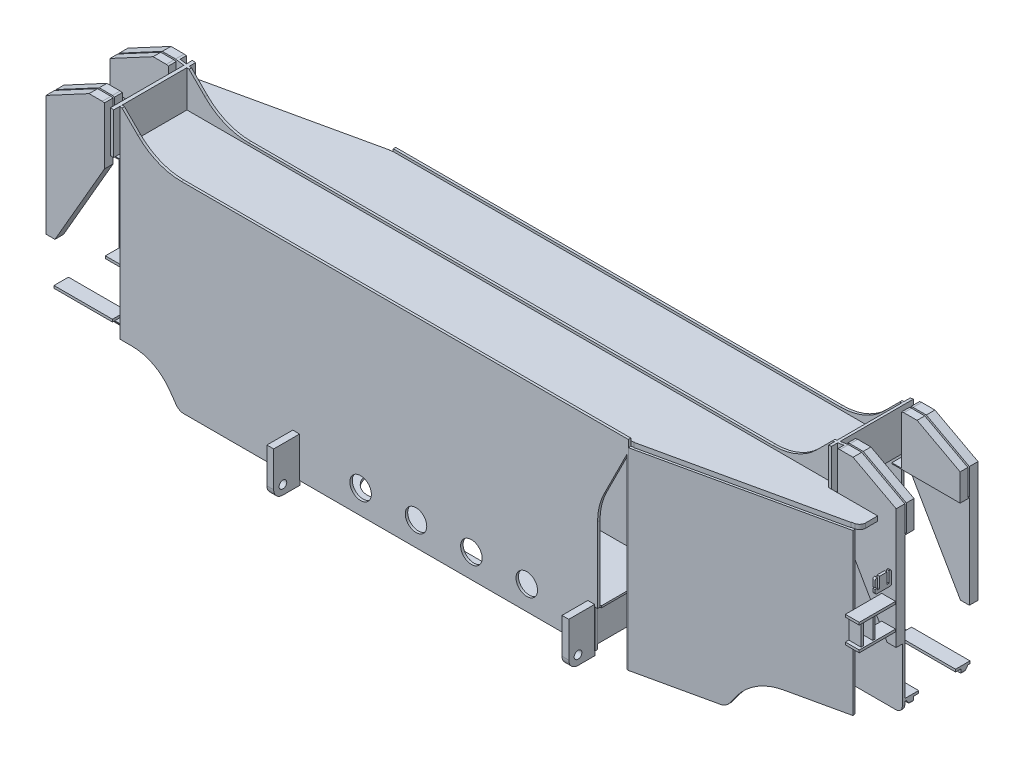
SolidWorks part; units mm, degrees
ref_plane "正面" through (0, 0, 0) normal (0, 0, 1) x (1, 0, 0)
ref_plane "平面" through (0, 0, 0) normal (0, 1, 0) x (1, 0, 0)
ref_plane "右側面" through (0, 0, 0) normal (1, 0, 0) x (0, 0, -1)
ref_plane "平面1" through (0, 0, 238) normal (0, 0, 1) x (1, 0, 0)
sketch "ｽｹｯﾁ2" plane through (0, 0, 238) normal (0, 0, 1) x (1, 0, 0)
  line L0 (20, 120) -> (259.781, 119.9998)
  line L1 (382.7741, 55.8641) -> (403.0452, 26.8271)
  line L2 (427.644, 13.9998) -> (2117.356, 13.9998)
  line L3 (2141.9548, 26.8271) -> (2162.2259, 55.8641)
  line L4 (2285.219, 119.9998) -> (2525, 120)
  line L5 (2545, 140) -> (2545, 315.36)
  line L6 (2545, 315.36) -> (2545, 706)
  line L7 (2545, 706) -> (2405, 781)
  line L8 (2405, 781) -> (2362, 781)
  line L9 (2362, 781) -> (2318, 774)
  line L10 (2318, 774) -> (2266.5789, 722.5791)
  line L11 (2125.157, 663.9999) -> (419.843, 663.9999)
  line L12 (278.4211, 722.5791) -> (227, 774)
  line L13 (227, 774) -> (183, 781)
  line L14 (183, 781) -> (140, 781)
  line L15 (140, 781) -> (0, 706)
  line L16 (0, 706) -> (0, 315.36)
  line L17 (0, 315.36) -> (0, 140)
  arc A0 (0, 140) -> (20, 120) centre (20, 140) ccw
  arc A1 (259.781, 119.9998) -> (382.7741, 55.8641) centre (259.781, -30) cw
  arc A2 (403.0452, 26.8271) -> (427.644, 13.9998) centre (427.644, 44) ccw
  arc A3 (2117.356, 13.9998) -> (2141.9548, 26.8271) centre (2117.356, 44) ccw
  arc A4 (2162.2259, 55.8641) -> (2285.219, 119.9998) centre (2285.219, -30) cw
  arc A5 (2525, 120) -> (2545, 140) centre (2525, 140) ccw
  arc A6 (2266.5789, 722.5791) -> (2125.157, 663.9999) centre (2125.157, 864) cw
  arc A7 (419.843, 663.9999) -> (278.4211, 722.5791) centre (419.843, 864) cw
extrude "ﾎﾞｽ - 押し出し1" add sketch "ｽｹｯﾁ2" along normal blind 8
sketch "ｽｹｯﾁ3" plane through (0, 0, 238) normal (0, 0, 1) x (1, 0, 0)
  line L0 (1072.5, 297) -> (1472.5, 297)
  line L1 (1472.5, 497) -> (1072.5, 497)
  circle A0 centre (972.5, 92) radius 35
  circle A1 centre (1272.5, 92) radius 35
  circle A2 centre (1572.5, 92) radius 35
  arc A3 (1472.5, 297) -> (1572.5, 397) centre (1472.5, 397) ccw
  arc A4 (1572.5, 397) -> (1472.5, 497) centre (1472.5, 397) ccw
  arc A5 (1072.5, 497) -> (972.5, 397) centre (1072.5, 397) ccw
  arc A6 (972.5, 397) -> (1072.5, 297) centre (1072.5, 397) ccw
  circle A7 centre (50, 499) radius 20.25
  circle A8 centre (2495, 499) radius 20.25
  circle A9 centre (27, 401.5) radius 10.5
  circle A10 centre (2518, 401.5) radius 10.5
sketch "ｽｹｯﾁ4" plane through (0, 0, 238) normal (0, 0, 1) x (1, 0, 0)
  line L0 (1072.5, 297) -> (1472.5, 297)
  line L1 (1472.5, 497) -> (1072.5, 497)
  circle A0 centre (972.5, 92) radius 35
  circle A1 centre (1272.5, 92) radius 35
  circle A2 centre (1572.5, 92) radius 35
  arc A3 (1472.5, 297) -> (1572.5, 397) centre (1472.5, 397) ccw
  arc A4 (1572.5, 397) -> (1472.5, 497) centre (1472.5, 397) ccw
  arc A5 (1072.5, 497) -> (972.5, 397) centre (1072.5, 397) ccw
  arc A6 (972.5, 397) -> (1072.5, 297) centre (1072.5, 397) ccw
  circle A7 centre (50, 499) radius 20.25
  circle A8 centre (2495, 499) radius 20.25
  circle A9 centre (27, 401.5) radius 10.5
  circle A10 centre (2518, 401.5) radius 10.5
extrude "ｶｯﾄ - 押し出し2" cut sketch "ｽｹｯﾁ4" along normal blind 8
ref_plane "平面2" through (0, 0, 20) normal (0, 0, 1) x (1, 0, 0)
sketch "ｽｹｯﾁ6" plane through (0, 0, 20) normal (0, 0, 1) x (1, 0, 0)
  line L0 (781, 14) -> (2117.356, 13.9998)
  line L1 (2141.9548, 26.8271) -> (2162.2259, 55.8641)
  line L2 (2285.219, 119.9998) -> (2325, 120)
  line L3 (2325, 120) -> (2325, 775.1136)
  line L4 (2325, 775.1136) -> (2318, 774)
  line L5 (2318, 774) -> (2266.5789, 722.5791)
  line L6 (2125.157, 663.9999) -> (672.5, 664)
  line L7 (672.5, 664) -> (672.5, 629)
  line L8 (672.5, 629) -> (751.3851, 471.2291)
  line L9 (772.4999, 381.786) -> (772.5, 138)
  line L10 (772.5, 138) -> (781, 138)
  line L11 (781, 138) -> (781, 14)
  arc A0 (2117.356, 13.9998) -> (2141.9548, 26.8271) centre (2117.356, 44) ccw
  arc A1 (2162.2259, 55.8641) -> (2285.219, 119.9998) centre (2285.219, -30) cw
  arc A2 (2266.5789, 722.5791) -> (2125.157, 663.9999) centre (2125.157, 864) cw
  arc A3 (751.3851, 471.2291) -> (772.4999, 381.786) centre (572.5, 381.786) cw
extrude "ﾎﾞｽ - 押し出し2" add sketch "ｽｹｯﾁ6" along normal blind 8
sketch "ｽｹｯﾁ7" plane through (0, 0, 20) normal (0, 0, 1) x (1, 0, 0)
  circle A0 centre (1002.5, 92) radius 35
  circle A1 centre (1182.5, 92) radius 35
  circle A2 centre (1362.5, 92) radius 35
  circle A3 centre (1542.5, 92) radius 35
sketch "ｽｹｯﾁ8" plane through (0, 0, 20) normal (0, 0, 1) x (1, 0, 0)
  circle A0 centre (1002.5, 92) radius 35
  circle A1 centre (1182.5, 92) radius 35
  circle A2 centre (1362.5, 92) radius 35
  circle A3 centre (1542.5, 92) radius 35
extrude "ｶｯﾄ - 押し出し4" cut sketch "ｽｹｯﾁ8" along normal blind 8
ref_plane "平面3" through (0, 0, 456) normal (0, 0, 1) x (1, 0, 0)
sketch "ｽｹｯﾁ10" plane through (0, 0, 456) normal (0, 0, 1) x (1, 0, 0)
  line L0 (1764, 14) -> (1764, 138)
  line L1 (1764, 138) -> (1772.5, 138)
  line L2 (1772.5, 138) -> (1772.5001, 381.786)
  line L3 (1793.6149, 471.2291) -> (1872.5, 629)
  line L4 (1872.5, 629) -> (1872.5, 664)
  line L5 (1872.5, 664) -> (419.843, 663.9999)
  line L6 (278.4211, 722.5791) -> (227, 774)
  line L7 (227, 774) -> (220, 775.1136)
  line L8 (220, 775.1136) -> (220, 120)
  line L9 (220, 120) -> (259.781, 119.9998)
  line L10 (382.7741, 55.8641) -> (403.0452, 26.8271)
  line L11 (427.644, 13.9998) -> (1764, 14)
  arc A0 (1772.5001, 381.786) -> (1793.6149, 471.2291) centre (1972.5, 381.786) cw
  arc A1 (419.843, 663.9999) -> (278.4211, 722.5791) centre (419.843, 864) cw
  arc A2 (259.781, 119.9998) -> (382.7741, 55.8641) centre (259.781, -30) cw
  arc A3 (403.0452, 26.8271) -> (427.644, 13.9998) centre (427.644, 44) ccw
extrude "ﾎﾞｽ - 押し出し3" add sketch "ｽｹｯﾁ10" along normal blind 8
sketch "ｽｹｯﾁ11" plane through (0, 0, 456) normal (0, 0, 1) x (1, 0, 0)
  circle A0 centre (1002.5, 92) radius 35
  circle A1 centre (1182.5, 92) radius 35
  circle A2 centre (1362.5, 92) radius 35
  circle A3 centre (1542.5, 92) radius 35
sketch "ｽｹｯﾁ12" plane through (0, 0, 456) normal (0, 0, 1) x (1, 0, 0)
  circle A0 centre (1002.5, 92) radius 35
  circle A1 centre (1182.5, 92) radius 35
  circle A2 centre (1362.5, 92) radius 35
  circle A3 centre (1542.5, 92) radius 35
extrude "ｶｯﾄ - 押し出し6" cut sketch "ｽｹｯﾁ12" along normal blind 8
ref_plane "平面4" through (0, 14, 0) normal (0, 1, 0) x (1, 0, 0)
sketch "ｽｹｯﾁ14" plane through (0, 14, 0) normal (0, 1, 0) x (1, 0, 0)
  line L0 (678.3594, -26.7085) -> (75.7, -159.54)
  line L1 (75.7, -159.54) -> (73.9781, -151.7275)
  line L2 (73.9781, -151.7275) -> (671.6288, -20)
  line L3 (671.6288, -20) -> (676.8807, -20)
  line L4 (676.8807, -20) -> (678.3594, -26.7085)
extrude "ﾎﾞｽ - 押し出し4" add sketch "ｽｹｯﾁ14" along normal blind 626.98
sketch "ｽｹｯﾁ15" plane through (0, 14, 0) normal (0, 1, 0) x (1, 0, 0)
  line L0 (1866.6406, -457.2915) -> (2469.3, -324.46)
  line L1 (2469.3, -324.46) -> (2471.0219, -332.2725)
  line L2 (2471.0219, -332.2725) -> (1873.3712, -464)
  line L3 (1873.3712, -464) -> (1868.1193, -464)
  line L4 (1868.1193, -464) -> (1866.6406, -457.2915)
extrude "ﾎﾞｽ - 押し出し5" add sketch "ｽｹｯﾁ15" along normal blind 626.98
ref_plane "平面5" through (0, 600, 0) normal (0, 1, 0) x (1, 0, 0)
sketch "ｽｹｯﾁ17" plane through (0, 600, 0) normal (0, 1, 0) x (1, 0, 0)
  line L0 (662.5192, -29.1759) -> (85.2504, -156.411)
  line L1 (85.2504, -156.411) -> (85.6808, -158.3641)
  line L2 (85.6808, -158.3641) -> (662.9496, -31.129)
  line L3 (662.9496, -31.129) -> (662.5192, -29.1759)
extrude "ﾎﾞｽ - 押し出し6" add sketch "ｽｹｯﾁ17" along normal blind 56
sketch "ｽｹｯﾁ18" plane through (0, 600, 0) normal (0, 1, 0) x (1, 0, 0)
  line L0 (1882.4808, -454.8241) -> (2459.7496, -327.589)
  line L1 (2459.7496, -327.589) -> (2459.3192, -325.6359)
  line L2 (2459.3192, -325.6359) -> (1882.0504, -452.871)
  line L3 (1882.0504, -452.871) -> (1882.4808, -454.8241)
extrude "ﾎﾞｽ - 押し出し7" add sketch "ｽｹｯﾁ18" along normal blind 56
ref_plane "平面6" through (0, 641, 0) normal (0, 1, 0) x (1, 0, 0)
sketch "ｽｹｯﾁ20" plane through (0, 641, 0) normal (0, 1, 0) x (1, 0, 0)
  line L0 (672.5, -28) -> (75.7206, -159.5325)
  line L1 (59.9974, -179.072) -> (60, -218)
  line L2 (60, -218) -> (220, -218)
  line L3 (220, -218) -> (220, -238)
  line L4 (220, -238) -> (2324.98, -238)
  line L5 (2324.98, -238) -> (2324.98, -28)
  line L6 (2324.98, -28) -> (672.5, -28)
  arc A0 (75.7206, -159.5325) -> (59.9974, -179.072) centre (80, -179.072) ccw
extrude "ﾎﾞｽ - 押し出し8" add sketch "ｽｹｯﾁ20" along normal blind 15
sketch "ｽｹｯﾁ21" plane through (0, 641, 0) normal (0, 1, 0) x (1, 0, 0)
  line L0 (1872.5, -456) -> (2469.2794, -324.4675)
  line L1 (2485.0026, -304.928) -> (2485, -266)
  line L2 (2485, -266) -> (2325, -266)
  line L3 (2325, -266) -> (2325, -246)
  line L4 (2325, -246) -> (220.02, -246)
  line L5 (220.02, -246) -> (220.02, -456)
  line L6 (220.02, -456) -> (1872.5, -456)
  arc A0 (2469.2794, -324.4675) -> (2485.0026, -304.928) centre (2465, -304.928) ccw
extrude "ﾎﾞｽ - 押し出し9" add sketch "ｽｹｯﾁ21" along normal blind 15
ref_plane "平面7" through (0, 22, 0) normal (0, 1, 0) x (1, 0, 0)
sketch "ｽｹｯﾁ23" plane through (0, 22, 0) normal (0, 1, 0) x (1, 0, 0)
  line L0 (804, -28) -> (2098.5, -28)
  line L1 (2098.5, -28) -> (2098.5, -238)
  line L2 (2098.5, -238) -> (804, -238)
  line L3 (804, -238) -> (804, -28)
extrude "ﾎﾞｽ - 押し出し10" add sketch "ｽｹｯﾁ23" along normal blind 8
sketch "ｽｹｯﾁ24" plane through (0, 22, 0) normal (0, 1, 0) x (1, 0, 0)
  line L0 (1202, -73) -> (1342, -73)
  line L1 (1342, -193) -> (1202, -193)
  circle A0 centre (972, -133) radius 60
  circle A1 centre (1572, -133) radius 60
  circle A2 centre (1942, -133) radius 60
  arc A3 (1342, -73) -> (1402, -133) centre (1342, -133) cw
  arc A4 (1402, -133) -> (1342, -193) centre (1342, -133) cw
  arc A5 (1202, -193) -> (1142, -133) centre (1202, -133) cw
  arc A6 (1142, -133) -> (1202, -73) centre (1202, -133) cw
sketch "ｽｹｯﾁ25" plane through (0, 22, 0) normal (0, 1, 0) x (1, 0, 0)
  line L0 (1202, -73) -> (1342, -73)
  line L1 (1342, -193) -> (1202, -193)
  circle A0 centre (972, -133) radius 60
  circle A1 centre (1572, -133) radius 60
  circle A2 centre (1942, -133) radius 60
  arc A3 (1342, -73) -> (1402, -133) centre (1342, -133) cw
  arc A4 (1402, -133) -> (1342, -193) centre (1342, -133) cw
  arc A5 (1202, -193) -> (1142, -133) centre (1202, -133) cw
  arc A6 (1142, -133) -> (1202, -73) centre (1202, -133) cw
extrude "ｶｯﾄ - 押し出し8" cut sketch "ｽｹｯﾁ25" along normal blind 8
sketch "ｽｹｯﾁ26" plane through (0, 22, 0) normal (0, 1, 0) x (1, 0, 0)
  line L0 (446.5, -246) -> (1741, -246)
  line L1 (1741, -246) -> (1741, -456)
  line L2 (1741, -456) -> (446.5, -456)
  line L3 (446.5, -456) -> (446.5, -246)
extrude "ﾎﾞｽ - 押し出し11" add sketch "ｽｹｯﾁ26" along normal blind 8
sketch "ｽｹｯﾁ27" plane through (0, 22, 0) normal (0, 1, 0) x (1, 0, 0)
  line L0 (1203, -291) -> (1343, -291)
  line L1 (1343, -411) -> (1203, -411)
  circle A0 centre (603, -351) radius 60
  circle A1 centre (973, -351) radius 60
  circle A2 centre (1573, -351) radius 60
  arc A3 (1343, -291) -> (1403, -351) centre (1343, -351) cw
  arc A4 (1403, -351) -> (1343, -411) centre (1343, -351) cw
  arc A5 (1203, -411) -> (1143, -351) centre (1203, -351) cw
  arc A6 (1143, -351) -> (1203, -291) centre (1203, -351) cw
extrude "ｶｯﾄ - 押し出し9" cut sketch "ｽｹｯﾁ27" along normal blind 8
ref_plane "平面8" through (0, 138, 0) normal (0, 1, 0) x (1, 0, 0)
sketch "ｽｹｯﾁ29" plane through (0, 138, 0) normal (0, 1, 0) x (1, 0, 0)
  line L0 (768, -28) -> (1712, -28)
  line L1 (1712, -28) -> (1712, -238)
  line L2 (1712, -238) -> (768, -238)
  line L3 (768, -238) -> (768, -28)
extrude "ﾎﾞｽ - 押し出し12" add sketch "ｽｹｯﾁ29" along normal blind 6
sketch "ｽｹｯﾁ30" plane through (0, 138, 0) normal (0, 1, 0) x (1, 0, 0)
  line L0 (833, -246) -> (1777, -246)
  line L1 (1777, -246) -> (1777, -456)
  line L2 (1777, -456) -> (833, -456)
  line L3 (833, -456) -> (833, -246)
extrude "ﾎﾞｽ - 押し出し13" add sketch "ｽｹｯﾁ30" along normal blind 6
ref_plane "平面9" through (0, 0, 218) normal (0, 0, 1) x (1, 0, 0)
sketch "ｽｹｯﾁ32" plane through (0, 0, 218) normal (0, 0, 1) x (1, 0, 0)
  line L0 (0, 315.36) -> (29.1052, 315.36)
  line L1 (29.1052, 315.36) -> (190, 594.038)
  line L2 (190, 594.038) -> (190, 779.8864)
  line L3 (190, 779.8864) -> (183, 781)
  line L4 (183, 781) -> (140, 781)
  line L5 (140, 781) -> (0, 706)
  line L6 (0, 706) -> (0, 315.36)
extrude "ﾎﾞｽ - 押し出し14" add sketch "ｽｹｯﾁ32" along normal blind 20
ref_plane "平面10" through (0, 0, 464) normal (0, 0, 1) x (1, 0, 0)
sketch "ｽｹｯﾁ34" plane through (0, 0, 464) normal (0, 0, 1) x (1, 0, 0)
  line L0 (0, 315.36) -> (29.1052, 315.36)
  line L1 (29.1052, 315.36) -> (190, 594.038)
  line L2 (190, 594.038) -> (190, 779.8864)
  line L3 (190, 779.8864) -> (183, 781)
  line L4 (183, 781) -> (140, 781)
  line L5 (140, 781) -> (0, 706)
  line L6 (0, 706) -> (0, 315.36)
extrude "ﾎﾞｽ - 押し出し15" add sketch "ｽｹｯﾁ34" along normal blind 20
sketch "ｽｹｯﾁ35" plane through (0, 0, 0) normal (0, 0, 1) x (1, 0, 0)
  line L0 (2545, 315.36) -> (2545, 706)
  line L1 (2545, 706) -> (2405, 781)
  line L2 (2405, 781) -> (2362, 781)
  line L3 (2362, 781) -> (2355, 779.8864)
  line L4 (2355, 779.8864) -> (2355, 594.038)
  line L5 (2355, 594.038) -> (2515.8948, 315.36)
  line L6 (2515.8948, 315.36) -> (2545, 315.36)
extrude "ﾎﾞｽ - 押し出し16" add sketch "ｽｹｯﾁ35" along normal blind 20
ref_plane "平面11" through (0, 0, 246) normal (0, 0, 1) x (1, 0, 0)
sketch "ｽｹｯﾁ37" plane through (0, 0, 246) normal (0, 0, 1) x (1, 0, 0)
  line L0 (2545, 315.36) -> (2545, 706)
  line L1 (2545, 706) -> (2405, 781)
  line L2 (2405, 781) -> (2362, 781)
  line L3 (2362, 781) -> (2355, 779.8864)
  line L4 (2355, 779.8864) -> (2355, 594.038)
  line L5 (2355, 594.038) -> (2515.8948, 315.36)
  line L6 (2515.8948, 315.36) -> (2545, 315.36)
extrude "ﾎﾞｽ - 押し出し17" add sketch "ｽｹｯﾁ37" along normal blind 20
ref_plane "平面12" through (0, 0, 20) normal (0, 0, 1) x (1, 0, 0)
sketch "ｽｹｯﾁ39" plane through (0, 0, 20) normal (0, 0, 1) x (1, 0, 0)
  line L0 (2545, 315.36) -> (2545, 706)
  line L1 (2545, 706) -> (2405, 781)
  line L2 (2405, 781) -> (2362, 781)
  line L3 (2362, 781) -> (2355, 779.8864)
  line L4 (2355, 779.8864) -> (2355, 594.038)
  line L5 (2355, 594.038) -> (2515.8948, 315.36)
  line L6 (2515.8948, 315.36) -> (2545, 315.36)
extrude "ﾎﾞｽ - 押し出し18" add sketch "ｽｹｯﾁ39" along normal blind 8
ref_plane "平面13" through (0, 0, 456) normal (0, 0, 1) x (1, 0, 0)
sketch "ｽｹｯﾁ41" plane through (0, 0, 456) normal (0, 0, 1) x (1, 0, 0)
  line L0 (0, 315.36) -> (29.1052, 315.36)
  line L1 (29.1052, 315.36) -> (190, 594.038)
  line L2 (190, 594.038) -> (190, 779.8864)
  line L3 (190, 779.8864) -> (183, 781)
  line L4 (183, 781) -> (140, 781)
  line L5 (140, 781) -> (0, 706)
  line L6 (0, 706) -> (0, 315.36)
extrude "ﾎﾞｽ - 押し出し19" add sketch "ｽｹｯﾁ41" along normal blind 8
ref_plane "平面14" through (0, 0, 251) normal (0, 0, 1) x (1, 0, 0)
sketch "ｽｹｯﾁ43" plane through (0, 0, 251) normal (0, 0, 1) x (1, 0, 0)
  line L0 (0, 620.82) -> (190, 620.82)
  line L1 (190, 620.82) -> (190, 779.8864)
  line L2 (190, 779.8864) -> (183, 781)
  line L3 (183, 781) -> (140, 781)
  line L4 (140, 781) -> (0, 706)
  line L5 (0, 706) -> (0, 620.82)
extrude "ﾎﾞｽ - 押し出し20" add sketch "ｽｹｯﾁ43" along normal blind 25
ref_plane "平面15" through (0, 0, 426) normal (0, 0, 1) x (1, 0, 0)
sketch "ｽｹｯﾁ45" plane through (0, 0, 426) normal (0, 0, 1) x (1, 0, 0)
  line L0 (0, 620.82) -> (190, 620.82)
  line L1 (190, 620.82) -> (190, 779.8864)
  line L2 (190, 779.8864) -> (183, 781)
  line L3 (183, 781) -> (140, 781)
  line L4 (140, 781) -> (0, 706)
  line L5 (0, 706) -> (0, 620.82)
extrude "ﾎﾞｽ - 押し出し21" add sketch "ｽｹｯﾁ45" along normal blind 25
ref_plane "平面16" through (0, 0, 33) normal (0, 0, 1) x (1, 0, 0)
sketch "ｽｹｯﾁ47" plane through (0, 0, 33) normal (0, 0, 1) x (1, 0, 0)
  line L0 (2545, 620.82) -> (2545, 706)
  line L1 (2545, 706) -> (2405, 781)
  line L2 (2405, 781) -> (2362, 781)
  line L3 (2362, 781) -> (2355, 779.8864)
  line L4 (2355, 779.8864) -> (2355, 620.82)
  line L5 (2355, 620.82) -> (2545, 620.82)
extrude "ﾎﾞｽ - 押し出し22" add sketch "ｽｹｯﾁ47" along normal blind 25
ref_plane "平面17" through (0, 0, 208) normal (0, 0, 1) x (1, 0, 0)
sketch "ｽｹｯﾁ49" plane through (0, 0, 208) normal (0, 0, 1) x (1, 0, 0)
  line L0 (2545, 620.82) -> (2545, 706)
  line L1 (2545, 706) -> (2405, 781)
  line L2 (2405, 781) -> (2362, 781)
  line L3 (2362, 781) -> (2355, 779.8864)
  line L4 (2355, 779.8864) -> (2355, 620.82)
  line L5 (2355, 620.82) -> (2545, 620.82)
extrude "ﾎﾞｽ - 押し出し23" add sketch "ｽｹｯﾁ49" along normal blind 25
sketch "ｽｹｯﾁ50" plane through (0, 0, 246) normal (0, 0, 1) x (1, 0, 0)
  line L0 (0, 617.82) -> (190, 617.82)
  line L1 (190, 617.82) -> (190, 620.82)
  line L2 (190, 620.82) -> (0, 620.82)
  line L3 (0, 620.82) -> (0, 617.82)
extrude "ﾎﾞｽ - 押し出し24" add sketch "ｽｹｯﾁ50" along normal blind 30
sketch "ｽｹｯﾁ51" plane through (0, 0, 426) normal (0, 0, 1) x (1, 0, 0)
  line L0 (0, 617.82) -> (222, 617.82)
  line L1 (222, 617.82) -> (222, 620.82)
  line L2 (222, 620.82) -> (0, 620.82)
  line L3 (0, 620.82) -> (0, 617.82)
extrude "ﾎﾞｽ - 押し出し25" add sketch "ｽｹｯﾁ51" along normal blind 32
ref_plane "平面18" through (0, 0, 26) normal (0, 0, 1) x (1, 0, 0)
sketch "ｽｹｯﾁ53" plane through (0, 0, 26) normal (0, 0, 1) x (1, 0, 0)
  line L0 (2323, 617.82) -> (2545, 617.82)
  line L1 (2545, 617.82) -> (2545, 620.82)
  line L2 (2545, 620.82) -> (2323, 620.82)
  line L3 (2323, 620.82) -> (2323, 617.82)
extrude "ﾎﾞｽ - 押し出し26" add sketch "ｽｹｯﾁ53" along normal blind 32
sketch "ｽｹｯﾁ54" plane through (0, 0, 208) normal (0, 0, 1) x (1, 0, 0)
  line L0 (2355, 617.82) -> (2545, 617.82)
  line L1 (2545, 617.82) -> (2545, 620.82)
  line L2 (2545, 620.82) -> (2355, 620.82)
  line L3 (2355, 620.82) -> (2355, 617.82)
extrude "ﾎﾞｽ - 押し出し27" add sketch "ｽｹｯﾁ54" along normal blind 30
sketch "ｽｹｯﾁ55" plane through (0, 0, 0) normal (1, 0, 0) x (0, 0, -1)
  line L0 (-251.6, 150) -> (-450.4, 150)
  line L1 (-450.4, 150) -> (-450.4, 149)
  line L2 (-450.4, 149) -> (-442.698, 138)
  line L3 (-442.698, 138) -> (-259.302, 138)
  line L4 (-259.302, 138) -> (-251.6, 149)
  line L5 (-251.6, 149) -> (-251.6, 150)
extrude "ﾎﾞｽ - 押し出し28" add sketch "ｽｹｯﾁ55" along normal blind 346.3065
sketch "ｽｹｯﾁ56" plane through (0, 138, 0) normal (0, 1, 0) x (1, 0, 0)
  line L0 (-10, -273.771) -> (155, -273.771)
  line L1 (195, -313.771) -> (195, -388.229)
  line L2 (155, -428.229) -> (-10, -428.229)
  line L3 (-10, -428.229) -> (-10, -273.771)
  arc A0 (155, -273.771) -> (195, -313.771) centre (155, -313.771) cw
  arc A1 (195, -388.229) -> (155, -428.229) centre (155, -388.229) cw
sketch "ｽｹｯﾁ57" plane through (0, 138, 0) normal (0, 1, 0) x (1, 0, 0)
  line L0 (-10, -273.771) -> (155, -273.771)
  line L1 (195, -313.771) -> (195, -388.229)
  line L2 (155, -428.229) -> (-10, -428.229)
  line L3 (-10, -428.229) -> (-10, -273.771)
  arc A0 (155, -273.771) -> (195, -313.771) centre (155, -313.771) cw
  arc A1 (195, -388.229) -> (155, -428.229) centre (155, -388.229) cw
extrude "ｶｯﾄ - 押し出し11" cut sketch "ｽｹｯﾁ57" along normal blind 12
ref_plane "平面19" through (2545, 0, 0) normal (1, 0, 0) x (0, 0, -1)
sketch "ｽｹｯﾁ59" plane through (2545, 0, 0) normal (1, 0, 0) x (0, 0, -1)
  line L0 (-232.4, 150) -> (-232.4, 149)
  line L1 (-232.4, 149) -> (-224.698, 138)
  line L2 (-224.698, 138) -> (-41.302, 138)
  line L3 (-41.302, 138) -> (-33.6, 149)
  line L4 (-33.6, 149) -> (-33.6, 150)
  line L5 (-33.6, 150) -> (-232.4, 150)
extrude "ﾎﾞｽ - 押し出し29" add sketch "ｽｹｯﾁ59" against normal blind 346.3065
sketch "ｽｹｯﾁ60" plane through (0, 138, 0) normal (0, 1, 0) x (1, 0, 0)
  line L0 (2555, -210.229) -> (2390, -210.229)
  line L1 (2350, -170.229) -> (2350, -95.771)
  line L2 (2390, -55.771) -> (2555, -55.771)
  line L3 (2555, -55.771) -> (2555, -210.229)
  arc A0 (2390, -210.229) -> (2350, -170.229) centre (2390, -170.229) cw
  arc A1 (2350, -95.771) -> (2390, -55.771) centre (2390, -95.771) cw
extrude "ｶｯﾄ - 押し出し12" cut sketch "ｽｹｯﾁ60" along normal blind 12
ref_plane "平面20" through (0, 150, 0) normal (0, 1, 0) x (1, 0, 0)
sketch "ｽｹｯﾁ62" plane through (0, 150, 0) normal (0, 1, 0) x (1, 0, 0)
  line L0 (0, -244) -> (190, -244)
  line L1 (190, -244) -> (190, -291)
  line L2 (190, -291) -> (0, -291)
  line L3 (0, -291) -> (0, -244)
  line L4 (0, -411) -> (190, -411)
  line L5 (190, -411) -> (190, -458)
  line L6 (190, -458) -> (0, -458)
  line L7 (0, -458) -> (0, -411)
  line L8 (215.708, -244) -> (833, -244)
  line L9 (833, -244) -> (833, -291)
  line L10 (833, -291) -> (215.708, -291)
  line L11 (215.708, -291) -> (215.708, -244)
  line L12 (215.708, -411) -> (833, -411)
  line L13 (833, -411) -> (833, -458)
  line L14 (833, -458) -> (215.708, -458)
  line L15 (215.708, -458) -> (215.708, -411)
extrude "ﾎﾞｽ - 押し出し30" add sketch "ｽｹｯﾁ62" along normal blind 8
sketch "ｽｹｯﾁ63" plane through (0, 150, 0) normal (0, 1, 0) x (1, 0, 0)
  line L0 (1712, -193) -> (2329.292, -193)
  line L1 (2329.292, -193) -> (2329.292, -240)
  line L2 (2329.292, -240) -> (1712, -240)
  line L3 (1712, -240) -> (1712, -193)
  line L4 (1712, -26) -> (2329.292, -26)
  line L5 (2329.292, -26) -> (2329.292, -73)
  line L6 (2329.292, -73) -> (1712, -73)
  line L7 (1712, -73) -> (1712, -26)
  line L8 (2355, -193) -> (2545, -193)
  line L9 (2545, -193) -> (2545, -240)
  line L10 (2545, -240) -> (2355, -240)
  line L11 (2355, -240) -> (2355, -193)
  line L12 (2355, -26) -> (2545, -26)
  line L13 (2545, -26) -> (2545, -73)
  line L14 (2545, -73) -> (2355, -73)
  line L15 (2355, -73) -> (2355, -26)
extrude "ﾎﾞｽ - 押し出し31" add sketch "ｽｹｯﾁ63" along normal blind 8
ref_plane "平面21" through (1771.5, 0, 0) normal (1, 0, 0) x (0, 0, -1)
sketch "ｽｹｯﾁ65" plane through (1771.5, 0, 0) normal (1, 0, 0) x (0, 0, -1)
  line L0 (-28, 30) -> (-40.32, 29.97)
  line L1 (-40.32, 29.97) -> (-63.75, 129.12)
  line L2 (-63.75, 129.12) -> (-53.54, 138)
  line L3 (-53.54, 138) -> (-28, 30)
extrude "ﾎﾞｽ - 押し出し32" add sketch "ｽｹｯﾁ65" along normal blind 319
sketch "ｽｹｯﾁ66" plane through (1771.5, 0, 0) normal (1, 0, 0) x (0, 0, -1)
  line L0 (-212.46, 138) -> (-202.25, 129.12)
  line L1 (-202.25, 129.12) -> (-225.68, 29.97)
  line L2 (-225.68, 29.97) -> (-238, 30)
  line L3 (-238, 30) -> (-212.46, 138)
extrude "ﾎﾞｽ - 押し出し33" add sketch "ｽｹｯﾁ66" along normal blind 319
ref_plane "平面22" through (454.5, 0, 0) normal (1, 0, 0) x (0, 0, -1)
sketch "ｽｹｯﾁ68" plane through (454.5, 0, 0) normal (1, 0, 0) x (0, 0, -1)
  line L0 (-430.46, 138) -> (-420.25, 129.12)
  line L1 (-420.25, 129.12) -> (-443.68, 29.97)
  line L2 (-443.68, 29.97) -> (-456, 30)
  line L3 (-456, 30) -> (-430.46, 138)
extrude "ﾎﾞｽ - 押し出し34" add sketch "ｽｹｯﾁ68" along normal blind 319
sketch "ｽｹｯﾁ69" plane through (454.5, 0, 0) normal (1, 0, 0) x (0, 0, -1)
  line L0 (-246, 30) -> (-258.32, 29.97)
  line L1 (-258.32, 29.97) -> (-281.75, 129.12)
  line L2 (-281.75, 129.12) -> (-271.54, 138)
  line L3 (-271.54, 138) -> (-246, 30)
extrude "ﾎﾞｽ - 押し出し35" add sketch "ｽｹｯﾁ69" along normal blind 319
sketch "ｽｹｯﾁ70" plane through (0, 0, 0) normal (0, 0, 1) x (1, 0, 0)
  line L0 (-80, -80) -> (2625, -80)
  line L1 (2625, -80) -> (2625, 860)
  line L2 (2625, 860) -> (-80, 860)
  line L3 (-80, 860) -> (-80, -80)
  line L4 (20, 120) -> (259.781, 119.9998)
  line L5 (382.7741, 55.8641) -> (403.0452, 26.8271)
  line L6 (427.644, 13.9998) -> (2117.356, 13.9998)
  line L7 (2141.9548, 26.8271) -> (2162.2259, 55.8641)
  line L8 (2285.219, 119.9998) -> (2525, 120)
  line L9 (2545, 140) -> (2545, 315.36)
  line L10 (2545, 315.36) -> (2545, 706)
  line L11 (2545, 706) -> (2405, 781)
  line L12 (2405, 781) -> (2362, 781)
  line L13 (2362, 781) -> (2318, 774)
  line L14 (2318, 774) -> (2266.5789, 722.5791)
  line L15 (2125.157, 663.9999) -> (419.843, 663.9999)
  line L16 (278.4211, 722.5791) -> (227, 774)
  line L17 (227, 774) -> (183, 781)
  line L18 (183, 781) -> (140, 781)
  line L19 (140, 781) -> (0, 706)
  line L20 (0, 706) -> (0, 315.36)
  line L21 (0, 315.36) -> (0, 140)
  arc A0 (0, 140) -> (20, 120) centre (20, 140) ccw
  arc A1 (259.781, 119.9998) -> (382.7741, 55.8641) centre (259.781, -30) cw
  arc A2 (403.0452, 26.8271) -> (427.644, 13.9998) centre (427.644, 44) ccw
  arc A3 (2117.356, 13.9998) -> (2141.9548, 26.8271) centre (2117.356, 44) ccw
  arc A4 (2162.2259, 55.8641) -> (2285.219, 119.9998) centre (2285.219, -30) cw
  arc A5 (2525, 120) -> (2545, 140) centre (2525, 140) ccw
  arc A6 (2266.5789, 722.5791) -> (2125.157, 663.9999) centre (2125.157, 864) cw
  arc A7 (419.843, 663.9999) -> (278.4211, 722.5791) centre (419.843, 864) cw
sketch "ｽｹｯﾁ71" plane through (0, 0, 0) normal (0, 0, 1) x (1, 0, 0)
  line L0 (-80, -80) -> (2625, -80)
  line L1 (2625, -80) -> (2625, 860)
  line L2 (2625, 860) -> (-80, 860)
  line L3 (-80, 860) -> (-80, -80)
  line L4 (20, 120) -> (259.781, 119.9998)
  line L5 (382.7741, 55.8641) -> (403.0452, 26.8271)
  line L6 (427.644, 13.9998) -> (2117.356, 13.9998)
  line L7 (2141.9548, 26.8271) -> (2162.2259, 55.8641)
  line L8 (2285.219, 119.9998) -> (2525, 120)
  line L9 (2545, 140) -> (2545, 315.36)
  line L10 (2545, 315.36) -> (2545, 706)
  line L11 (2545, 706) -> (2405, 781)
  line L12 (2405, 781) -> (2362, 781)
  line L13 (2362, 781) -> (2318, 774)
  line L14 (2318, 774) -> (2266.5789, 722.5791)
  line L15 (2125.157, 663.9999) -> (419.843, 663.9999)
  line L16 (278.4211, 722.5791) -> (227, 774)
  line L17 (227, 774) -> (183, 781)
  line L18 (183, 781) -> (140, 781)
  line L19 (140, 781) -> (0, 706)
  line L20 (0, 706) -> (0, 315.36)
  line L21 (0, 315.36) -> (0, 140)
  arc A0 (0, 140) -> (20, 120) centre (20, 140) ccw
  arc A1 (259.781, 119.9998) -> (382.7741, 55.8641) centre (259.781, -30) cw
  arc A2 (403.0452, 26.8271) -> (427.644, 13.9998) centre (427.644, 44) ccw
  arc A3 (2117.356, 13.9998) -> (2141.9548, 26.8271) centre (2117.356, 44) ccw
  arc A4 (2162.2259, 55.8641) -> (2285.219, 119.9998) centre (2285.219, -30) cw
  arc A5 (2525, 120) -> (2545, 140) centre (2525, 140) ccw
  arc A6 (2266.5789, 722.5791) -> (2125.157, 663.9999) centre (2125.157, 864) cw
  arc A7 (419.843, 663.9999) -> (278.4211, 722.5791) centre (419.843, 864) cw
extrude "ｶｯﾄ - 押し出し14" cut sketch "ｽｹｯﾁ71" along normal blind 600
ref_plane "平面23" through (782, 0, 0) normal (1, 0, 0) x (0, 0, -1)
sketch "ｽｹｯﾁ73" plane through (782, 0, 0) normal (1, 0, 0) x (0, 0, -1)
  line L0 (-26, 29) -> (-240, 29)
  line L1 (-240, 29) -> (-240, 138)
  line L2 (-240, 138) -> (-26, 138)
  line L3 (-26, 138) -> (-26, 29)
  line L4 (-244, 29) -> (-458, 29)
  line L5 (-458, 29) -> (-458, 138)
  line L6 (-458, 138) -> (-244, 138)
  line L7 (-244, 138) -> (-244, 29)
  line L8 (-462, 0) -> (-518, 0)
  line L9 (-548, 30) -> (-548, 145)
  line L10 (-548, 145) -> (-462, 145)
  line L11 (-462, 145) -> (-462, 0)
  arc A0 (-518, 0) -> (-548, 30) centre (-518, 30) cw
extrude "ﾎﾞｽ - 押し出し36" add sketch "ｽｹｯﾁ73" along normal blind 22
sketch "ｽｹｯﾁ74" plane through (782, 0, 0) normal (1, 0, 0) x (0, 0, -1)
  circle A0 centre (-518, 30) radius 12.5
sketch "ｽｹｯﾁ75" plane through (782, 0, 0) normal (1, 0, 0) x (0, 0, -1)
  circle A0 centre (-518, 30) radius 12.5
extrude "ｶｯﾄ - 押し出し16" cut sketch "ｽｹｯﾁ75" along normal blind 22
ref_plane "平面24" through (1741, 0, 0) normal (1, 0, 0) x (0, 0, -1)
sketch "ｽｹｯﾁ77" plane through (1741, 0, 0) normal (1, 0, 0) x (0, 0, -1)
  line L0 (-26, 29) -> (-240, 29)
  line L1 (-240, 29) -> (-240, 138)
  line L2 (-240, 138) -> (-26, 138)
  line L3 (-26, 138) -> (-26, 29)
  line L4 (-244, 29) -> (-458, 29)
  line L5 (-458, 29) -> (-458, 138)
  line L6 (-458, 138) -> (-244, 138)
  line L7 (-244, 138) -> (-244, 29)
  line L8 (-462, 0) -> (-518, 0)
  line L9 (-548, 30) -> (-548, 145)
  line L10 (-548, 145) -> (-462, 145)
  line L11 (-462, 145) -> (-462, 0)
  arc A0 (-518, 0) -> (-548, 30) centre (-518, 30) cw
extrude "ﾎﾞｽ - 押し出し37" add sketch "ｽｹｯﾁ77" along normal blind 22
sketch "ｽｹｯﾁ78" plane through (1741, 0, 0) normal (1, 0, 0) x (0, 0, -1)
  circle A0 centre (-518, 30) radius 12.5
sketch "ｽｹｯﾁ79" plane through (1741, 0, 0) normal (1, 0, 0) x (0, 0, -1)
  circle A0 centre (-518, 30) radius 12.5
extrude "ｶｯﾄ - 押し出し18" cut sketch "ｽｹｯﾁ79" along normal blind 22
ref_plane "平面25" through (2, 0, 0) normal (1, 0, 0) x (0, 0, -1)
sketch "ｽｹｯﾁ81" plane through (2, 0, 0) normal (1, 0, 0) x (0, 0, -1)
  line L0 (-100, 358.5) -> (-218, 358.5)
  line L1 (-218, 358.5) -> (-218, 366.5)
  line L2 (-218, 366.5) -> (-100, 366.5)
  line L3 (-100, 366.5) -> (-100, 358.5)
  line L4 (-100, 436.5) -> (-218, 436.5)
  line L5 (-218, 436.5) -> (-218, 444.5)
  line L6 (-218, 444.5) -> (-100, 444.5)
  line L7 (-100, 444.5) -> (-100, 436.5)
extrude "ﾎﾞｽ - 押し出し38" add sketch "ｽｹｯﾁ81" along normal blind 45
ref_plane "平面26" through (7, 0, 0) normal (1, 0, 0) x (0, 0, -1)
sketch "ｽｹｯﾁ83" plane through (7, 0, 0) normal (1, 0, 0) x (0, 0, -1)
  line L0 (-111, 366.5) -> (-119, 366.5)
  line L1 (-119, 366.5) -> (-119, 436.5)
  line L2 (-119, 436.5) -> (-111, 436.5)
  line L3 (-111, 436.5) -> (-111, 366.5)
  line L4 (-149, 366.5) -> (-157, 366.5)
  line L5 (-157, 366.5) -> (-157, 436.5)
  line L6 (-157, 436.5) -> (-149, 436.5)
  line L7 (-149, 436.5) -> (-149, 366.5)
extrude "ﾎﾞｽ - 押し出し39" add sketch "ｽｹｯﾁ83" along normal blind 40
ref_plane "平面27" through (2498, 0, 0) normal (1, 0, 0) x (0, 0, -1)
sketch "ｽｹｯﾁ85" plane through (2498, 0, 0) normal (1, 0, 0) x (0, 0, -1)
  line L0 (-266, 358.5) -> (-384, 358.5)
  line L1 (-384, 358.5) -> (-384, 366.5)
  line L2 (-384, 366.5) -> (-266, 366.5)
  line L3 (-266, 366.5) -> (-266, 358.5)
  line L4 (-266, 436.5) -> (-384, 436.5)
  line L5 (-384, 436.5) -> (-384, 444.5)
  line L6 (-384, 444.5) -> (-266, 444.5)
  line L7 (-266, 444.5) -> (-266, 436.5)
extrude "ﾎﾞｽ - 押し出し40" add sketch "ｽｹｯﾁ85" along normal blind 45
sketch "ｽｹｯﾁ86" plane through (2498, 0, 0) normal (1, 0, 0) x (0, 0, -1)
  line L0 (-365, 366.5) -> (-373, 366.5)
  line L1 (-373, 366.5) -> (-373, 436.5)
  line L2 (-373, 436.5) -> (-365, 436.5)
  line L3 (-365, 436.5) -> (-365, 366.5)
  line L4 (-327, 366.5) -> (-335, 366.5)
  line L5 (-335, 366.5) -> (-335, 436.5)
  line L6 (-335, 436.5) -> (-327, 436.5)
  line L7 (-327, 436.5) -> (-327, 366.5)
extrude "ﾎﾞｽ - 押し出し41" add sketch "ｽｹｯﾁ86" along normal blind 40
ref_plane "平面28" through (15, 0, 0) normal (1, 0, 0) x (0, 0, -1)
sketch "ｽｹｯﾁ88" plane through (15, 0, 0) normal (1, 0, 0) x (0, 0, -1)
  line L0 (-170, 483) -> (-213, 483)
  line L1 (-218, 488) -> (-218, 523)
  line L2 (-213, 528) -> (-170, 528)
  line L3 (-165, 523) -> (-165, 488)
  arc A0 (-213, 483) -> (-218, 488) centre (-213, 488) cw
  arc A1 (-218, 523) -> (-213, 528) centre (-213, 523) cw
  arc A2 (-170, 528) -> (-165, 523) centre (-170, 523) cw
  arc A3 (-165, 488) -> (-170, 483) centre (-170, 488) cw
extrude "ﾎﾞｽ - 押し出し42" add sketch "ｽｹｯﾁ88" along normal blind 8
sketch "ｽｹｯﾁ89" plane through (15, 0, 0) normal (1, 0, 0) x (0, 0, -1)
  line L0 (-172, 493) -> (-179, 493)
  line L1 (-179, 493) -> (-179, 535)
  line L2 (-179, 535) -> (-172, 535)
  line L3 (-172, 535) -> (-172, 493)
  line L4 (-203, 493) -> (-210, 493)
  line L5 (-210, 493) -> (-210, 535)
  line L6 (-210, 535) -> (-203, 535)
  line L7 (-203, 535) -> (-203, 493)
sketch "ｽｹｯﾁ90" plane through (15, 0, 0) normal (1, 0, 0) x (0, 0, -1)
  line L0 (-172, 493) -> (-179, 493)
  line L1 (-179, 493) -> (-179, 535)
  line L2 (-179, 535) -> (-172, 535)
  line L3 (-172, 535) -> (-172, 493)
  line L4 (-203, 493) -> (-210, 493)
  line L5 (-210, 493) -> (-210, 535)
  line L6 (-210, 535) -> (-203, 535)
  line L7 (-203, 535) -> (-203, 493)
extrude "ｶｯﾄ - 押し出し20" cut sketch "ｽｹｯﾁ90" along normal blind 8
sketch "ｽｹｯﾁ91" plane through (15, 0, 0) normal (1, 0, 0) x (0, 0, -1)
  circle A0 centre (-166, 500) radius 2.5
extrude "ｶｯﾄ - 押し出し21" cut sketch "ｽｹｯﾁ91" along normal blind 8
ref_plane "平面29" through (2522, 0, 0) normal (1, 0, 0) x (0, 0, -1)
sketch "ｽｹｯﾁ93" plane through (2522, 0, 0) normal (1, 0, 0) x (0, 0, -1)
  line L0 (-271, 483) -> (-314, 483)
  line L1 (-319, 488) -> (-319, 523)
  line L2 (-314, 528) -> (-271, 528)
  line L3 (-266, 523) -> (-266, 488)
  arc A0 (-314, 483) -> (-319, 488) centre (-314, 488) cw
  arc A1 (-319, 523) -> (-314, 528) centre (-314, 523) cw
  arc A2 (-271, 528) -> (-266, 523) centre (-271, 523) cw
  arc A3 (-266, 488) -> (-271, 483) centre (-271, 488) cw
extrude "ﾎﾞｽ - 押し出し43" add sketch "ｽｹｯﾁ93" along normal blind 8
sketch "ｽｹｯﾁ94" plane through (2522, 0, 0) normal (1, 0, 0) x (0, 0, -1)
  line L0 (-305, 493) -> (-312, 493)
  line L1 (-312, 493) -> (-312, 535)
  line L2 (-312, 535) -> (-305, 535)
  line L3 (-305, 535) -> (-305, 493)
  line L4 (-274, 493) -> (-281, 493)
  line L5 (-281, 493) -> (-281, 535)
  line L6 (-281, 535) -> (-274, 535)
  line L7 (-274, 535) -> (-274, 493)
sketch "ｽｹｯﾁ95" plane through (2522, 0, 0) normal (1, 0, 0) x (0, 0, -1)
  line L0 (-305, 493) -> (-312, 493)
  line L1 (-312, 493) -> (-312, 535)
  line L2 (-312, 535) -> (-305, 535)
  line L3 (-305, 535) -> (-305, 493)
  line L4 (-274, 493) -> (-281, 493)
  line L5 (-281, 493) -> (-281, 535)
  line L6 (-281, 535) -> (-274, 535)
  line L7 (-274, 535) -> (-274, 493)
extrude "ｶｯﾄ - 押し出し23" cut sketch "ｽｹｯﾁ95" along normal blind 8
sketch "ｽｹｯﾁ96" plane through (2522, 0, 0) normal (1, 0, 0) x (0, 0, -1)
  circle A0 centre (-318, 500) radius 2.5
extrude "ｶｯﾄ - 押し出し24" cut sketch "ｽｹｯﾁ96" along normal blind 8
sketch "ｽｹｯﾁ97" plane through (0, 0, 218) normal (0, 0, 1) x (1, 0, 0)
  line L0 (210, 641) -> (219.98, 641)
  line L1 (219.98, 641) -> (219.98, 775.1168)
  line L2 (219.98, 775.1168) -> (210, 776.7045)
  line L3 (210, 776.7045) -> (210, 641)
extrude "ﾎﾞｽ - 押し出し44" add sketch "ｽｹｯﾁ97" along normal blind 266
sketch "ｽｹｯﾁ98" plane through (0, 0, 0) normal (0, 0, 1) x (1, 0, 0)
  line L0 (2325.02, 641) -> (2335, 641)
  line L1 (2335, 641) -> (2335, 776.7045)
  line L2 (2335, 776.7045) -> (2325.02, 775.1168)
  line L3 (2325.02, 775.1168) -> (2325.02, 641)
extrude "ﾎﾞｽ - 押し出し45" add sketch "ｽｹｯﾁ98" along normal blind 266
ref_plane "平面30" through (0, 0, 257) normal (0, 0, 1) x (1, 0, 0)
sketch "ｽｹｯﾁ100" plane through (0, 0, 257) normal (0, 0, 1) x (1, 0, 0)
  line L0 (412.1531, 22.0886) -> (421.9829, 28.9714)
  line L1 (421.9829, 28.9714) -> (344.9409, 139)
  line L2 (344.9409, 139) -> (330.2916, 139)
  line L3 (330.2916, 139) -> (412.1531, 22.0886)
extrude "ﾎﾞｽ - 押し出し46" add sketch "ｽｹｯﾁ100" along normal blind 188
ref_plane "平面31" through (0, 0, 351) normal (0, 0, 1) x (1, 0, 0)
sketch "ｽｹｯﾁ102" plane through (0, 0, 351) normal (0, 0, 1) x (1, 0, 0)
  line L0 (359.9091, 63.5757) -> (400.8669, 92.2543)
  line L1 (400.8669, 92.2543) -> (377.924, 125.0205)
  line L2 (377.924, 125.0205) -> (336.9662, 96.3419)
  line L3 (336.9662, 96.3419) -> (359.9091, 63.5757)
  line L4 (359.9091, 63.5757) -> (400.8669, 92.2543) construction
revolve "ｶｯﾄ - 回転1" cut sketch "ｽｹｯﾁ102" angle 360 about L4
ref_plane "平面32" through (0, 0, 39) normal (0, 0, 1) x (1, 0, 0)
sketch "ｽｹｯﾁ104" plane through (0, 0, 39) normal (0, 0, 1) x (1, 0, 0)
  line L0 (2214.7084, 139) -> (2200.0591, 139)
  line L1 (2200.0591, 139) -> (2123.0171, 28.9714)
  line L2 (2123.0171, 28.9714) -> (2132.8469, 22.0886)
  line L3 (2132.8469, 22.0886) -> (2214.7084, 139)
extrude "ﾎﾞｽ - 押し出し47" add sketch "ｽｹｯﾁ104" along normal blind 188
ref_plane "平面33" through (0, 0, 133) normal (0, 0, 1) x (1, 0, 0)
sketch "ｽｹｯﾁ106" plane through (0, 0, 133) normal (0, 0, 1) x (1, 0, 0)
  line L0 (2185.0909, 63.5757) -> (2144.1331, 92.2543)
  line L1 (2144.1331, 92.2543) -> (2121.1902, 59.4881)
  line L2 (2121.1902, 59.4881) -> (2162.148, 30.8095)
  line L3 (2162.148, 30.8095) -> (2185.0909, 63.5757)
  line L4 (2185.0909, 63.5757) -> (2144.1331, 92.2543) construction
revolve "ｶｯﾄ - 回転2" cut sketch "ｽｹｯﾁ106" angle 360 about L4
